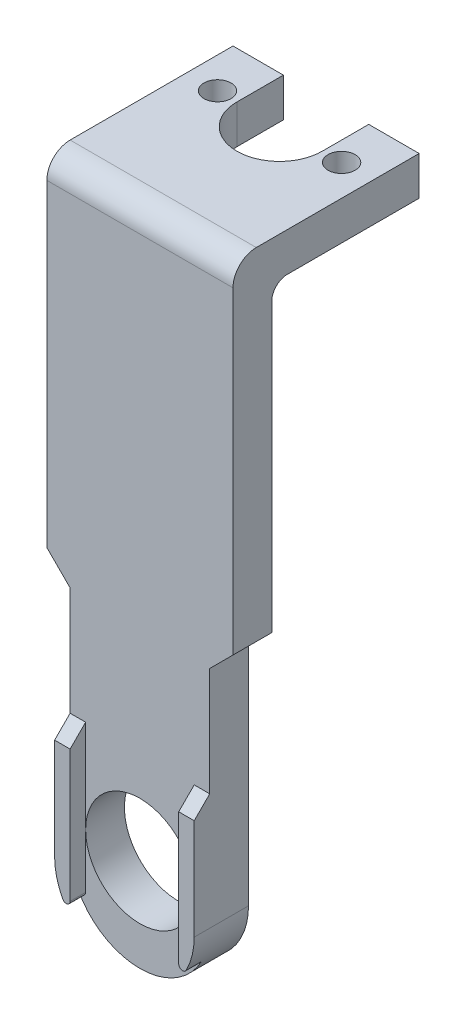
SolidWorks part; units mm, degrees
material "PMMA"
ref_plane "Front Plane" through (0, 0, 0) normal (0, 0, 1) x (1, 0, 0)
ref_plane "Top Plane" through (0, 0, 0) normal (0, 1, 0) x (1, 0, 0)
ref_plane "Right Plane" through (0, 0, 0) normal (1, 0, 0) x (0, 0, -1)
sketch "Sketch1" plane through (0, 0, 0) normal (0, 1, 0) x (1, 0, 0)
  line L1 (-12, 8) -> (-12, -18)
  line L2 (-12, -18) -> (12, -18)
  line L3 (12, -18) -> (12, 5.5)
  line L5 (-12, 8) -> (0, 8)
  line L6 (0, 8) -> (12, 8)
  line L7 (12, 8) -> (12, 5.5)
  line L8 (0, 8) -> (0, 0) construction
  line L9 (-17.0927, 0) -> (16.2972, 0) construction
  line L10 (0, 12.4942) -> (0, -10.971) construction
  line L11 (-8, 12.4942) -> (-8, -10.971) construction
  line L12 (8, 12.4942) -> (8, -10.971) construction
  circle A0 centre (0, 0) radius 5.5
  circle A1 centre (-8, 0) radius 1.75
  circle A2 centre (8, 0) radius 1.75
  dimension "D1" = 11
  dimension "D8" = 3.5
  dimension "D9" = 3.5
  dimension "D2" = 8
  dimension "D3" = 12
  dimension "D4" = 18
  dimension "D5" = 12
  dimension "D6" = 8
  dimension "D7" = 8
extrude "Boss-Extrude2" add sketch "Sketch1" along normal blind 5
sketch "Sketch2" plane through (0, 0, 0) normal (0, -1, 0) x (1, 0, 0)
  line L0 (-12, 18) -> (-12, 13)
  line L1 (-12, -8) -> (-12, 18) construction
  line L2 (-12, 13) -> (12, 13)
  line L3 (12, 18) -> (12, -8) construction
  line L4 (12, 13) -> (12, 18)
  line L5 (12, 18) -> (-12, 18)
  dimension "D1" = 5
extrude "Boss-Extrude3" add sketch "Sketch2" along normal blind 80
fillet "Fillet1" radius 3 1 edges at (0, 5, 18)
fillet "Fillet2" radius 2 1 edges at (0, 0, 13)
sketch "Sketch3" plane through (0, 0, 18) normal (0, 0, 1) x (1, 0, 0)
  line L0 (12, -80) -> (-12, -80) construction
  line L1 (0, 9.239) -> (0, -63.1826) construction
  circle A0 centre (0, -68) radius 7
  dimension "D1" = 14
  dimension "D2" = 12
extrude "Cut-Extrude1" cut sketch "Sketch3" against normal blind 60
sketch "Sketch4" plane through (0, 5, 0) normal (0, 1, 0) x (1, 0, 0)
  line L0 (-12, 8) -> (12, 8)
  line L1 (12, 8) -> (12, 6)
  line L2 (12, -15) -> (12, 8) construction
  line L3 (12, 6) -> (-12, 6)
  line L4 (-12, 8) -> (-12, -15) construction
  line L5 (-12, 6) -> (-12, 8)
  dimension "D1" = 2
extrude "Cut-Extrude2" cut sketch "Sketch4" against normal through all
sketch "Sketch5" plane through (0, 5, 0) normal (0, 1, 0) x (1, 0, 0)
  line L0 (-5.5, 0) -> (5.5, 0)
  line L1 (5.5, 0) -> (5.5, 6)
  line L2 (-12, 6) -> (12, 6) construction
  line L3 (5.5, 6) -> (-5.5, 6)
  line L4 (-5.5, 6) -> (-5.5, 0)
  circle A0 centre (0, 0) radius 5.5 construction
extrude "Cut-Extrude3" cut sketch "Sketch5" against normal through all
sketch "Sketch6" plane through (0, 0, 18) normal (0, 0, 1) x (1, 0, 0)
  line L0 (-12, -39) -> (-9, -42)
  line L1 (-12, 2) -> (-12, -80) construction
  line L2 (-9, -42) -> (-9, -80)
  line L3 (12, -80) -> (-12, -80) construction
  line L4 (-9, -80) -> (-12, -80)
  line L5 (-12, -80) -> (-12, -39)
  line L6 (0, 0) -> (0, -91.1725) construction
  line L7 (9, -80) -> (12, -80)
  line L8 (9, -42) -> (9, -80)
  line L9 (12, -39) -> (9, -42)
  line L10 (12, -80) -> (12, -39)
  dimension "D1" = 3
  dimension "D2" = 45
extrude "Cut-Extrude4" cut sketch "Sketch6" against normal through all
fillet "Fillet4" radius 9 2 edges at (9, -80, 15.5) (-9, -80, 15.5)
sketch "Sketch7" plane through (0, 0, 18) normal (0, 0, 1) x (1, 0, 0)
  line L0 (-7, -58) -> (-7, -76.6569)
  line L1 (-7, -58) -> (-9, -58)
  line L2 (-9, -71) -> (-9, -42) construction
  line L3 (-9, -58) -> (-9, -71)
  line L4 (0, -68) -> (-11.806, -68) construction
  line L5 (0, -59.1292) -> (0, -81.9536) construction
  line L6 (7, -58) -> (9, -58)
  line L7 (9, -58) -> (9, -71)
  line L8 (7, -58) -> (7, -76.6569)
  arc A0 (-9, -71) -> (-7, -76.6569) centre (0, -71) ccw
  arc A1 (9, -71) -> (7, -76.6569) centre (0, -71) cw
  dimension "D3" = 9
  dimension "D1" = 10
  dimension "D2" = 2
extrude "Boss-Extrude4" add sketch "Sketch7" along normal blind 2
chamfer "Chamfer1" distance 2 angle 45 2 edges at (8, -58, 18) (-8, -58, 18)
fillet "Fillet5" radius 0.5 2 edges at (7, -76.6569, 19) (-7, -76.6569, 19)
